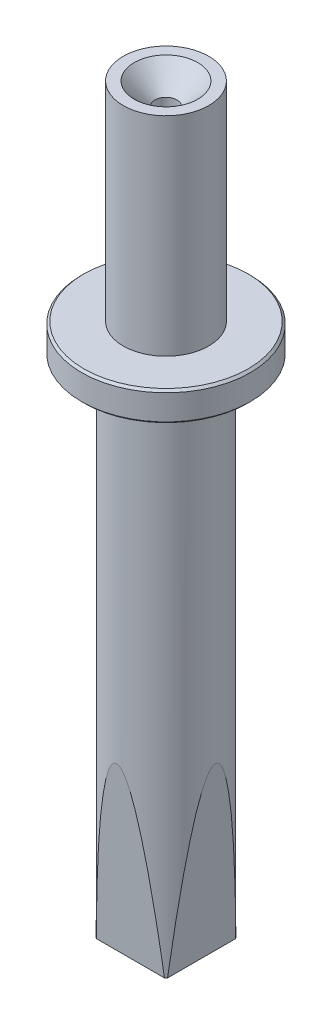
SolidWorks part; units mm, degrees
ref_plane "Спереди" through (0, 0, 0) normal (0, 0, 1) x (1, 0, 0)
ref_plane "Сверху" through (0, 0, 0) normal (0, 1, 0) x (1, 0, 0)
ref_plane "Справа" through (0, 0, 0) normal (1, 0, 0) x (0, 0, -1)
sketch "Эскиз1" plane through (0, 0, 0) normal (0, 1, 0) x (1, 0, 0)
  circle A0 centre (0, 0) radius 3.9
  dimension "D1" = 7.8
ref_plane "Плоскость1" through (0, -19, 0) normal (0, 1, 0) x (1, 0, 0)
extrude "Бобышка-Вытянуть1" add sketch "Эскиз1" against normal up to surface (19 mm away) up to plane "Плоскость1"
cosmetic thread "Условное изображение резьбы1" parameters "D2"=4.891
sketch "Эскиз3" plane through (0, -19, 0) normal (0, 1, 0) x (1, 0, 0)
  circle A0 centre (0, 0) radius 7.7
  dimension "D1" = 15.4
extrude "Бобышка-Вытянуть2" add sketch "Эскиз3" against normal blind 2.7 contours A0
ref_plane "Плоскость2" through (0, -21.7, 0) normal (0, -1, 0) x (-1, 0, 0)
sketch "Эскиз4" plane through (0, -21.7, 0) normal (0, -1, 0) x (-1, 0, 0)
  circle A0 centre (0, 0) radius 3.7
  dimension "D1" = 7.4
extrude "Бобышка-Вытянуть3" add sketch "Эскиз4" along normal blind 1
sketch "Эскиз5" plane through (0, -22.7, 0) normal (0, -1, 0) x (1, 0, 0)
  circle A0 centre (0, 0) radius 4.5
  dimension "D1" = 9
extrude "Бобышка-Вытянуть4" add sketch "Эскиз5" along normal blind 45
ref_plane "Плоскость3" through (0, -67.7, 0) normal (0, -1, 0) x (-1, 0, 0)
ref_plane "Плоскость4" through (0, -51.7, 0) normal (0, -1, 0) x (-1, 0, 0)
ref_plane "Плоскость5" through (4.5, 0, 0) normal (1, 0, 0) x (0, 0, -1)
sketch "Эскиз8" plane through (0, -51.7, 0) normal (0, -1, 0) x (-1, 0, 0)
  circle A0 centre (0, 0) radius 4.5 construction
  circle A1 centre (0, 0) radius 4.5
sketch "Эскиз9" plane through (0, 0, 0) normal (0, 0, 1) x (1, 0, 0)
  line L0 (4.5, -51.7) -> (3.25, -67.7)
  line L2 (-4.5, -51.7) -> (4.5, -51.7) construction
  line L3 (3.25, -67.7) -> (4.5, -67.7)
  line L4 (-4.5, -67.7) -> (4.5, -67.7) construction
  line L5 (-4.5, -67.7) -> (4.5, -67.7) construction
  line L6 (-4.5, -51.7) -> (4.5, -51.7) construction
  line L7 (4.5, -51.7) -> (4.5, -67.7) construction
  line L8 (4.5, -67.7) -> (4.5, -51.7)
  dimension "D1" = 1.25
extrude "Вырез-Вытянуть1" cut sketch "Эскиз9" against normal mid plane 29.5
pattern_circular "Круговой массив1" count 4 over 360 about axis through (0, -67.7, 0) along (0, 1, 0) of "Вырез-Вытянуть1" reverse direction yes
sketch "Эскиз10" plane through (0, -67.7, 0) normal (0, -1, 0) x (1, 0, 0)
  circle A0 centre (0, 0) radius 3.15
  dimension "D1" = 6.3
extrude "Вырез-Вытянуть2" cut sketch "Эскиз10" against normal blind 4
sketch "Эскиз11" plane through (0, -63.7, 0) normal (0, -1, 0) x (1, 0, 0)
  circle A0 centre (0, 0) radius 2.65
  circle A1 centre (0, 0) radius 3.15 construction
  dimension "D1" = 0.5
extrude "Вырез-Вытянуть3" cut sketch "Эскиз11" against normal up to surface (12 mm away) up to plane "Плоскость4"
sketch "Эскиз12" plane through (0, 0, 0) normal (0, 1, 0) x (1, 0, 0)
  circle A0 centre (0, 0) radius 2.9
  circle A1 centre (0, 0) radius 3.9 construction
  dimension "D1" = 1
ref_plane "Плоскость6" through (0, -2, 0) normal (0, 1, 0) x (1, 0, 0)
sketch "Эскиз13" plane through (0, -2, 0) normal (0, 1, 0) x (1, 0, 0)
  circle A0 centre (0, 0) radius 1
  dimension "D1" = 2
loft "Вырез-По сечениям1" cut profiles "Эскиз13", "Эскиз12" connector at (-0.6568, -2, -0.754) connector at (-1.9013, 0, -2.1897)
extrude "Вырез-Вытянуть4" cut sketch "Эскиз13<2>" against normal blind 3
sketch "Эскиз13<2>" plane through (0, -2, 0) normal (0, 1, 0) x (1, 0, 0) same geometry as "Эскиз13"
chamfer "Фаска1" distance 0.2 angle 45 2 edges at (0, -21.7, 7.7) (0, -19, 7.7)
